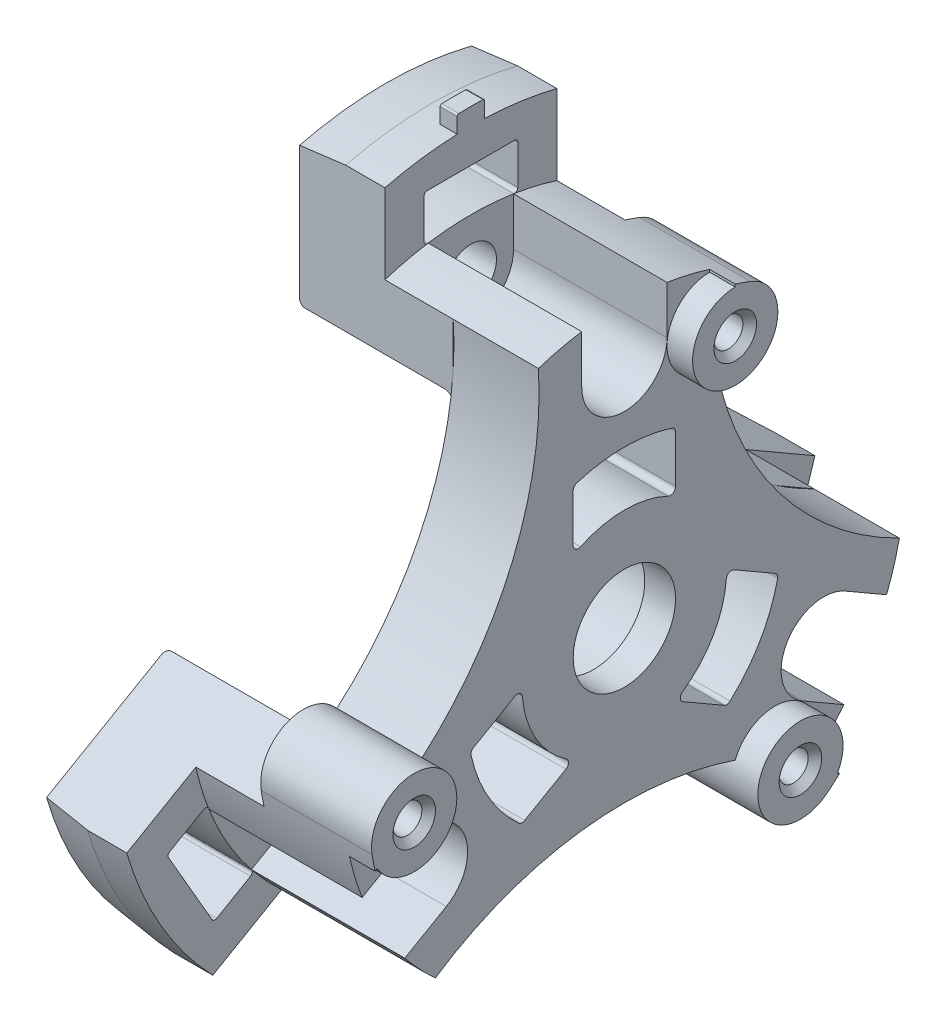
SolidWorks part; units mm, degrees
ref_plane "Front" through (0, 0, 0) normal (0, 0, 1) x (1, 0, 0)
ref_plane "Top" through (0, 0, 0) normal (0, 1, 0) x (1, 0, 0)
ref_plane "Right" through (0, 0, 0) normal (1, 0, 0) x (0, 0, -1)
sketch "草图1" plane through (0, 0, 0) normal (0, 0, 1) x (1, 0, 0)
  line L0 (-65.7429, 0) -> (89.5714, 0) construction
  line L1 (0, 67.1143) -> (0, -71.9143) construction
  line L2 (-7, 6) -> (-5, 6)
  line L3 (-5, 6) -> (-5, 16.5)
  line L4 (-5, 16.5) -> (0, 16.5)
  line L5 (0, 16.5) -> (0, 3)
  line L6 (-1.8, 3.975) -> (-7, 3.975)
  line L7 (-7, 3.975) -> (-7, 6)
  line L8 (-1.8, 3.975) -> (-1.8, 3)
  line L9 (-1.8, 3) -> (0, 3)
  dimension "D1" = 6
  dimension "D2" = 5.2
  dimension "D3" = 7.95
  dimension "D4" = 7
  dimension "D5" = 5
  dimension "D6" = 12
  dimension "D7" = 33
  dimension "D8" = 1.8
revolve "旋转1" add sketch "草图1" angle 360 about L0
sketch "草图2" plane through (-5, 0, 0) normal (-1, 0, 0) x (0, 0, 1)
  line L0 (-23.9515, 0) -> (26.381, 0) construction
  line L1 (0, 44.3891) -> (0, -20.5254) construction
  line L2 (0, 0) -> (-21.2641, -12.2768) construction
  line L3 (0, 0) -> (20.7932, -12.005) construction
  line L4 (0, 0) -> (-61.1055, 35.2793) construction
  line L5 (-5, 31.2128) -> (-5, 9) construction
  line L6 (5, 31.2128) -> (5, 9) construction
  circle A1 centre (-25, 14.4338) radius 20
  point P7 (0, 9)
  point P9 (-7.6795, 4.4338)
  dimension "D6" = 40
  dimension "D1" = 120
  dimension "D2" = 120
  dimension "D3" = 9
  dimension "D5" = 60
  dimension "D7" = 10
extrude "切除-拉伸1" cut sketch "草图2" against normal blind 10 contours A1
pattern_circular "阵列(圆周)1" count 3 over 360 about axis through (0, 0, 0) along (1, 0, 0) of "切除-拉伸1"
sketch "草图3" plane through (-5, 0, 0) normal (-1, 0, 0) x (0, 0, 1)
  line L0 (0, 18) -> (0, -12.9057) construction
  line L1 (-20.442, 0) -> (20.8303, 0) construction
  line L2 (-3, 8.4806) -> (-3, 5.6921)
  line L4 (3, 8.4806) -> (3, 5.6921)
  arc A0 (2.791, 8.7664) -> (-2.791, 8.7664) centre (0, 0) ccw
  circle A1 centre (0, 0) radius 6 construction
  arc A2 (2.5714, 5.421) -> (-2.5714, 5.421) centre (0, 0) ccw
  arc A3 (3, 5.6921) -> (2.5714, 5.421) centre (2.7, 5.6921) cw
  arc A4 (-2.5714, 5.421) -> (-3, 5.6921) centre (-2.7, 5.6921) cw
  arc A5 (3, 8.4806) -> (2.791, 8.7664) centre (2.7, 8.4806) ccw
  arc A6 (-2.791, 8.7664) -> (-3, 8.4806) centre (-2.7, 8.4806) ccw
  point P11 (3, 5.1962)
  point P16 (-3, 5.1962)
  point P19 (3, 8.6971)
  point P22 (-3, 8.6971)
  dimension "D1" = 9.2
  dimension "D3" = 0.3
  dimension "D2" = 6
extrude "切除-拉伸2" cut sketch "草图3" against normal blind 10
pattern_circular "阵列(圆周)2" count 3 over 360 about axis through (0, 0, 0) along (1, 0, 0) of "切除-拉伸2"
sketch "草图4" plane through (-5, 0, 0) normal (-1, 0, 0) x (0, 0, 1)
  line L0 (-16.7535, 0) -> (15.8993, 0) construction
  line L1 (0, 19.3876) -> (0, -16.6742) construction
  line L2 (-5.0408, 15.7111) -> (-5.0408, 11.9286)
  line L4 (5.0408, 11.9286) -> (5.0408, 15.7111)
  circle A0 centre (0, 0) radius 13.5 construction
  arc A1 (5.0408, 15.7111) -> (-5.0408, 15.7111) centre (0, 0) ccw construction
  arc A2 (5.0408, 15.7111) -> (-5.0408, 15.7111) centre (0, 0) ccw
  circle A3 centre (0, 13.5) radius 1.5
  arc A4 (-2.6744, 12.6708) -> (2.6744, 12.6708) centre (0, 13.5) ccw
  arc A5 (-2.6744, 12.6708) -> (-5.0408, 11.9286) centre (0, 0) ccw
  arc A6 (5.0408, 11.9286) -> (2.6744, 12.6708) centre (0, 0) ccw
  dimension "D1" = 27
  dimension "D2" = 3
  dimension "D4" = 5.6
  dimension "D5" = 25.9
extrude "凸台-拉伸1" add sketch "草图4" along normal blind 9
pattern_circular "阵列(圆周)3" count 3 over 360 about axis through (0, 0, 0) along (1, 0, 0) of "凸台-拉伸1"
sketch "草图5" plane through (-14, 0, 0) normal (-1, 0, 0) x (0, 0, 1)
  line L0 (-16.1323, 0) -> (16.637, 0) construction
  line L1 (0, 17.8058) -> (0, -12.3621) construction
  line L3 (-2.8, 12.6437) -> (-2.8, 9.2908)
  line L4 (-2.8, 9.2908) -> (2.8, 9.2908)
  line L5 (2.8, 12.6437) -> (2.8, 9.2908)
  arc A2 (2.8, 12.6437) -> (-2.8, 12.6437) centre (0, 0) ccw
  point P10 (0, 9.2908)
  point P11 (0, 13.55)
  dimension "D1" = 5.6
  dimension "D2" = 25.9
extrude "切除-拉伸3" cut sketch "草图5" against normal blind 1.7 contours L4 L5 A2 L3
sketch "草图10" plane through (-5, 0, 0) normal (-1, 0, 0) x (0, 0, 1)
  point P1 (0, 0)
  dimension "D1" = 12.8775
pattern_circular "阵列(圆周)4" count 3 over 360 about axis through (-65.7429, 0, 0) along (-1, 0, 0) of "切除-拉伸3"
sketch "草图6" plane through (0, 0, 0) normal (1, 0, 0) x (0, 0, -1)
  line L0 (-17.245, 0) -> (20.4566, 0) construction
  line L1 (0, 20.1005) -> (0, -14.3306) construction
  line L2 (-2.5, 16.3095) -> (-2.5, 13.5)
  line L3 (2.5, 16.3095) -> (2.5, 13.5)
  circle A0 centre (0, 0) radius 13.5 construction
  arc A1 (5.0408, 15.7111) -> (-5.0408, 15.7111) centre (0, 0) ccw construction
  arc A3 (2.5, 16.3095) -> (-2.5, 16.3095) centre (0, 0) ccw
  arc A4 (-2.5, 13.5) -> (2.5, 13.5) centre (0, 13.5) ccw
  dimension "D1" = 27
  dimension "D3" = 5
  dimension "D2" = 5
extrude "切除-拉伸4" cut sketch "草图6" against normal blind 9
pattern_circular "阵列(圆周)5" count 3 over 360 about axis through (0, 0, 0) along (1, 0, 0) of "切除-拉伸4"
sketch "草图7" plane through (-5, 0, 0) normal (-1, 0, 0) x (0, 0, 1)
  line L0 (0, 19.1221) -> (0, -13.8647) construction
  line L1 (16.0973, 0) -> (-17.961, 0) construction
  line L2 (-5, 15.5767) -> (-5, 15.7242)
  arc A1 (-5.8929, 15.4118) -> (-5, 15.5767) centre (-5, 13.0767) ccw
  circle A5 centre (0, 0) radius 14 construction
  arc A6 (-2.5, 16.3095) -> (-5.0408, 15.7111) centre (0, 0) ccw construction
  arc A7 (-5, 15.7242) -> (-5.8929, 15.4118) centre (0, 0) ccw
  point P7 (-5, 13.0767)
  dimension "D1" = 28
  dimension "D3" = 5
  dimension "D2" = 5
extrude "凸台-拉伸2" add sketch "草图7" against normal blind 6.5 contours A1 L2 A7
sketch "草图9" plane through (1.5, 0, 0) normal (1, 0, 0) x (0, 0, -1)
  line L0 (0, 17.5729) -> (0, -10.6538) construction
  line L1 (-14.0745, 0) -> (16.4041, 0) construction
  circle A0 centre (0, 0) radius 14 construction
  circle A1 centre (5, 13.0767) radius 0.85
  dimension "D1" = 1.7
extrude "切除-拉伸7" cut sketch "草图9" against normal blind 6.4 contours A1
chamfer "倒角3" distance 0.4 angle 45 1 edges at (1.5, 13.0767, -5.85)
pattern_circular "阵列(圆周)8" count 3 over 360 about axis through (0, 0, 0) along (1, 0, 0) of "凸台-拉伸2", "切除-拉伸7", "倒角3"
chamfer "倒角4" distance 0.5 angle 60 1 edges at (-7, 0, 3.975)
fillet "圆角6" radius 0.5 9 edges at (-5, 12.3565, -3.8754) (-5, 10.7, 0) (-5, 12.3565, 3.8754) (-5, -9.5345, -8.7633) (-5, -5.35, -9.2665) (-5, -2.822, -12.6388) (-5, -2.822, 12.6388) (-5, -5.35, 9.2665) (-5, -9.5345, 8.7633)
fillet "圆角7" radius 0.5 1 edges at (-7, 0, 6)
sketch "草图11" plane through (-14, 0, 0) normal (-1, 0, 0) x (0, 0, 1)
  line L0 (-24.0343, 0) -> (27.0991, 0) construction
  line L1 (0, 23.8854) -> (0, -19.7008) construction
  line L2 (-5.0408, 15.7111) -> (-5.0408, 20.386)
  line L3 (5.0408, 15.7111) -> (5.0408, 20.386)
  line L4 (-2.55, 19) -> (2.55, 19)
  line L5 (-2.75, 18.8) -> (-2.75, 16.2692)
  line L7 (2.75, 18.8) -> (2.75, 16.2692)
  arc A0 (5.0408, 20.386) -> (0, 21) centre (0, 0) ccw
  arc A1 (5.0408, 15.7111) -> (-5.0408, 15.7111) centre (0, 0) ccw construction
  arc A2 (5.0408, 15.7111) -> (2.75, 16.2692) centre (0, 0) ccw
  arc A3 (-2.75, 16.2692) -> (-5.0408, 15.7111) centre (0, 0) ccw
  arc A4 (0, 21) -> (-5.0408, 20.386) centre (0, 0) ccw
  arc A5 (2.75, 18.8) -> (2.55, 19) centre (2.55, 18.8) ccw
  arc A6 (-2.75, 18.8) -> (-2.55, 19) centre (-2.55, 18.8) cw
  point P15 (0, 17)
  point P16 (0, 19)
  point P18 (2.75, 19)
  point P20 (0, 22)
  point P23 (-2.75, 19)
  dimension "D1" = 42
  dimension "D4" = 0.2
  dimension "D2" = 5.5
  dimension "D3" = 19
extrude "凸台-拉伸3" add sketch "草图11" against normal up to surface (5 mm away) up to face at (-9, 13.5, -1.5)
pattern_circular "阵列(圆周)9" count 3 over 360 about axis through (0, 0, 0) along (1, 0, 0) of "凸台-拉伸3"
sketch "草图12" plane through (-9, 0, 0) normal (1, 0, 0) x (0, 0, -1)
  line L0 (0, 23.0537) -> (0, -15.9342) construction
  line L1 (-23.5138, 0) -> (22.1093, 0) construction
  line L2 (-0.8, 21.8888) -> (-0.8, 20.9848)
  line L3 (0.8, 21.8888) -> (0.8, 20.9848)
  arc A0 (0.7032, 21.9888) -> (-0.7032, 21.9888) centre (0, 0) ccw
  arc A1 (5.0408, 20.386) -> (-5.0408, 20.386) centre (0, 0) ccw construction
  arc A2 (0.8, 20.9848) -> (-0.8, 20.9848) centre (0, 0) ccw
  arc A3 (-22, 0) -> (22, 0) centre (0, 0) ccw
  arc A4 (-0.8, 21.8888) -> (-0.7032, 21.9888) centre (-0.7, 21.8888) cw
  arc A5 (0.7032, 21.9888) -> (0.8, 21.8888) centre (0.7, 21.8888) cw
  dimension "D2" = 1
  dimension "D3" = 0.1
  dimension "D1" = 1.6
extrude "凸台-拉伸4" add sketch "草图12" against normal blind 1 contours A0 A4 L2 A2 L3 A5
pattern_circular "阵列(圆周)10" [suppressed] count 3 over 360
fillet "圆角9" radius 0.3 6 edges at (-14, 12.5387, -3.2378) (-14, 12.5387, 3.2378) (-14, -9.0734, -9.2399) (-14, -3.4653, -12.4777) (-14, -3.4653, 12.4777) (-14, -9.0734, 9.2399)
fillet "圆角10" radius 0.2 6 edges at (-11.5, 16.2692, -2.75) (-11.5, 16.2692, 2.75) (-11.5, -10.5162, -12.7146) (-11.5, -5.753, -15.4646) (-11.5, -5.753, 15.4646) (-11.5, -10.5162, 12.7146)
sketch "草图14" plane through (0, 0, 0) normal (0, 0, 1) x (1, 0, 0)
  line L0 (6.5511, 0) -> (-13.5644, 0) construction
  line L1 (-11.2016, 4) -> (3.5999, 4) construction
  line L2 (-7.4213, 4.75) -> (-6.809, 4.75)
  line L3 (-6.809, 4.75) -> (-6.134, 4.075)
  line L4 (-6.134, 4.075) -> (-2.6377, 4.075)
  line L5 (-2.6377, 4.075) -> (-2.6377, 4)
  line L6 (-2.6377, 4) -> (-7.4213, 4)
  line L7 (-7.4213, 4) -> (-7.4213, 4.75)
  dimension "D1" = 4
  dimension "D2" = 0.15
  dimension "D3" = 1.5
  dimension "D4" = 45
revolve "切除-旋转1" [suppressed] cut sketch "草图14" angle 360 about L1
pattern_circular "阵列(圆周)11" [suppressed] count 4 over 360
sketch "草图15" plane through (0, 0, 0) normal (0, 0, 1) x (1, 0, 0)
  line L0 (8.389, 0) -> (-25.6839, 0) construction
  line L1 (0, 24.288) -> (0, -16.6697) construction
  line L2 (-11.3, 22.5255) -> (-11.3, 9.7426) construction
  line L4 (-14, 12.2537) -> (-14, 20.386) construction
  line L5 (-16.1078, 21) -> (-11.3, 21)
  line L6 (-11.3, 21) -> (-16.1078, 20.4097)
  line L7 (-16.1078, 20.4097) -> (-16.1078, 21)
  dimension "D1" = 2.7
  dimension "D2" = 21
  dimension "D3" = 7
revolve "切除-旋转2" cut sketch "草图15" angle 360 about L0
